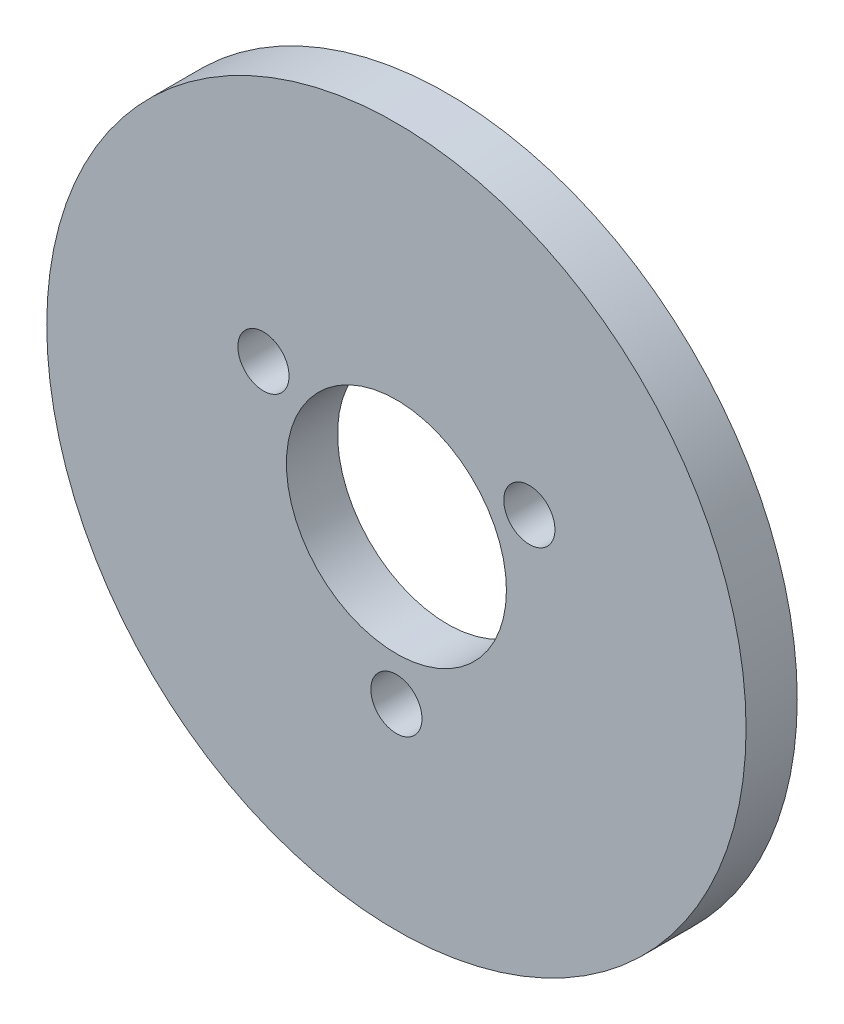
SolidWorks part; units mm, degrees
material "Acrylic (Medium-high impact)"
ref_plane "Front Plane" through (0, 0, 0) normal (0, 0, 1) x (1, 0, 0)
ref_plane "Top Plane" through (0, 0, 0) normal (0, 1, 0) x (1, 0, 0)
ref_plane "Right Plane" through (0, 0, 0) normal (1, 0, 0) x (0, 0, -1)
sketch "Sketch1" plane through (0, 0, 0) normal (0, 0, 1) x (1, 0, 0)
  circle A0 centre (0, 0) radius 20.5
  circle A1 centre (0, 0) radius 6.45
  dimension "D1" = 41
  dimension "D2" = 12.9
extrude "Boss-Extrude1" add sketch "Sketch1" along normal blind 3
sketch "Sketch2" plane through (0, 0, 0) normal (0, 0, -1) x (-1, 0, 0)
  circle A1 centre (7.7942, 4.5) radius 1.5
  circle A2 centre (7.7942, 4.5) radius 1.5
  circle A3 centre (-7.7942, 4.5) radius 1.5
  circle A4 centre (-7.7942, 4.5) radius 1.5
  circle A5 centre (0, -9) radius 1.5
  circle A6 centre (0, -9) radius 1.5
  dimension "D1" = 0
  dimension "D2" = 0
  dimension "D3" = 0
extrude "Cut-Extrude1" cut sketch "Sketch2" against normal through all
equation "\"smallPulleyTeeth\"= 30"
equation "\"largePulleyTeeth\"= 30"
equation "\"eighthThick\"= 3.0mm"
equation "\"sixteenthThick\" = 1.7mm"
equation "\"quarterThick\"=6.0mm"
equation "\"D1@Boss-Extrude1\"=\"eighthThick\""
